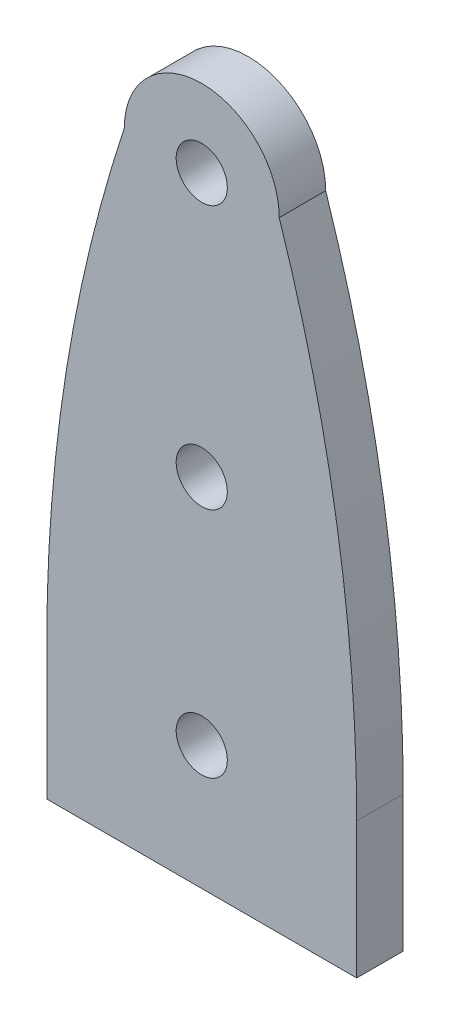
SolidWorks part; units mm, degrees
material "Thornel Mat VMA"
ref_plane "前视基准面" through (0, 0, 0) normal (0, 0, 1) x (1, 0, 0)
ref_plane "上视基准面" through (0, 0, 0) normal (0, 1, 0) x (1, 0, 0)
ref_plane "右视基准面" through (0, 0, 0) normal (1, 0, 0) x (0, 0, -1)
sketch "草图1" plane through (0, 0, 0) normal (0, 0, 1) x (1, 0, 0)
  line L0 (0, 0) -> (20, 0)
  line L1 (20, 0) -> (20, 40)
  line L2 (0, 40) -> (0, 0)
  line L3 (10, 0) -> (10, 40) construction
  arc A0 (20, 40) -> (0, 40) centre (10, 40) ccw
  circle A1 centre (10, 40) radius 1.65
  circle A2 centre (10, 8) radius 1.65
  circle A3 centre (10, 23) radius 1.65
  dimension "D1" = 3.3
  dimension "D2" = 20
  dimension "D3" = 40
  dimension "D4" = 15
  dimension "D5" = 8
extrude "凸台-拉伸1" add sketch "草图1" along normal blind 3
sketch "草图4" plane through (0, 0, 3) normal (0, 0, 1) x (1, 0, 0)
  line L0 (0, 40) -> (5, 40)
  line L1 (15, 40) -> (20, 40)
  arc A0 (20, 40) -> (0, 40) centre (10, 40) ccw
  arc A1 (15, 40) -> (5, 40) centre (10, 40) ccw
  arc A2 (20, 40) -> (0, 40) centre (10, 40) ccw construction
  dimension "D1" = 5
extrude "切除-拉伸3" cut sketch "草图4" against normal blind 28
fillet "圆角1" radius 100 2 edges at (20, 40, 1.5) (0, 40, 1.5)
